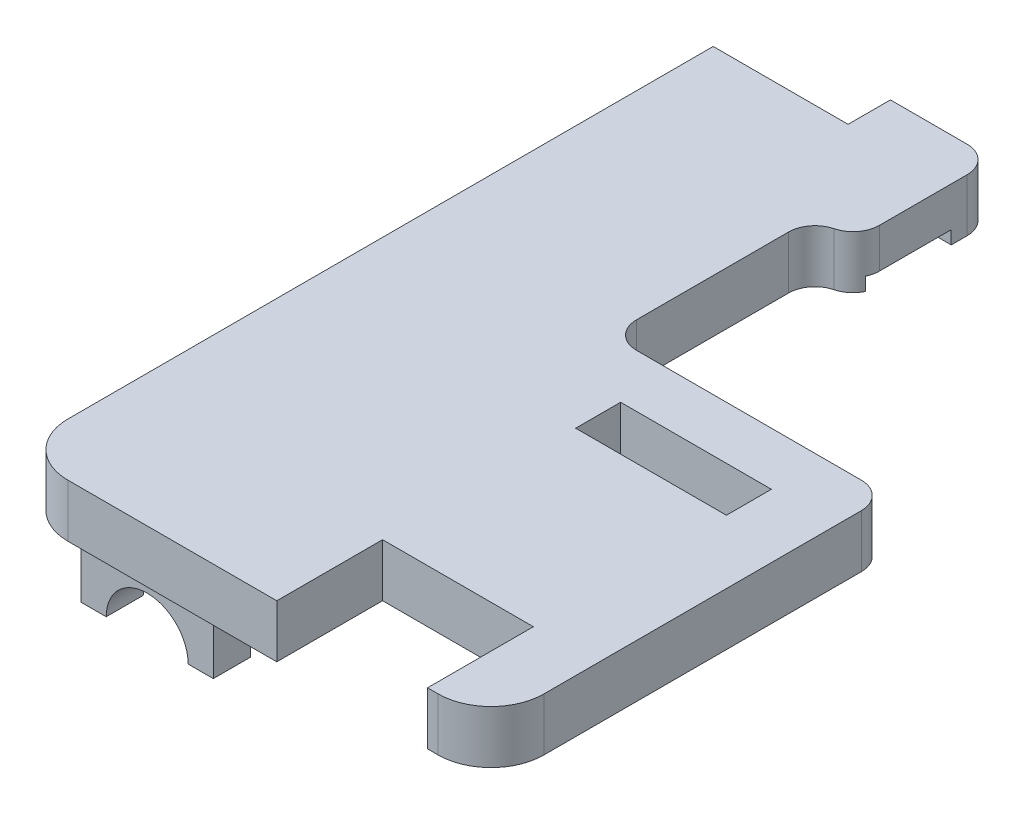
SolidWorks part; units mm, degrees
ref_plane "Front" through (0, 0, 0) normal (0, 0, 1) x (1, 0, 0)
ref_plane "Top" through (0, 0, 0) normal (0, 1, 0) x (1, 0, 0)
ref_plane "Right" through (0, 0, 0) normal (1, 0, 0) x (0, 0, -1)
sketch "Sketch1" plane through (0, 0, 0) normal (0, 1, 0) x (1, 0, 0)
  line L1 (0, 0) -> (18, 0)
  line L2 (0, 0) -> (0, 28)
  line L3 (0, 28) -> (18, 28)
  line L4 (18, 0) -> (18, 28)
  dimension "D1" = 18
  dimension "D2" = 28
extrude "Boss-Extrude1" add sketch "Sketch1" along normal blind 2 contours L2 L3 L4 L1
sketch "Sketch2" plane through (0, 0, 0) normal (0, -1, 0) x (1, 0, 0)
  line L0 (0, -28) -> (0, 0) construction
  line L1 (0, -2.5) -> (5, -2.5)
  line L2 (0, -2.5) -> (0, -3.9)
  line L3 (0, -3.9) -> (5, -3.9)
  line L4 (5, -2.5) -> (5, -3.9)
  line L5 (0, 0) -> (18, 0) construction
  line L6 (0, -16.3) -> (5, -16.3)
  line L7 (0, -16.3) -> (0, -14.9)
  line L8 (0, -14.9) -> (5, -14.9)
  line L9 (5, -16.3) -> (5, -14.9)
  dimension "D1" = 5
  dimension "D2" = 1.4
  dimension "D3" = 1.4
  dimension "D4" = 11
  dimension "D5" = 2.5
extrude "Boss-Extrude2" add sketch "Sketch2" along normal blind 4.25
sketch "Sketch4" plane through (0, 0, 0) normal (0, 0, 1) x (1, 0, 0)
  line L0 (5, -4.25) -> (0, -4.25) construction
  circle A0 centre (2.5, -4.25) radius 1.55
  dimension "D1" = 3.1
extrude "Cut-Extrude1" cut sketch "Sketch4" against normal through all both and the other way through all
fillet "Fillet1" radius 2 1 edges at (0, 1, 0)
sketch "Sketch5" plane through (0, 2, 0) normal (0, 1, 0) x (1, 0, 0)
  line L0 (2, 0) -> (18, 0) construction
  line L1 (9.9, 13) -> (15.6, 13)
  line L2 (9.9, 13) -> (9.9, 11.3)
  line L3 (9.9, 11.3) -> (15.6, 11.3)
  line L4 (15.6, 13) -> (15.6, 11.3)
  line L5 (15.6, 4) -> (9.9, 4)
  line L6 (15.6, 4) -> (15.6, 0)
  line L7 (15.6, 0) -> (9.9, 0)
  line L8 (9.9, 4) -> (9.9, 0)
  line L9 (15.5, 3.9) -> (15.5, 0) construction
  line L10 (10, 3.9) -> (10, 0) construction
  line L11 (15.5, 3.9) -> (10, 3.9) construction
  line L12 (10, 11.4) -> (15.5, 11.4) construction
  line L14 (15.5, 12.9) -> (10, 12.9) construction
  line L15 (5.1, 26.4) -> (0, 26.4)
  line L16 (5.1, 26.4) -> (5.1, 28)
  line L17 (5.1, 28) -> (0, 28)
  line L18 (0, 26.4) -> (0, 28)
  dimension "D1" = 0.1
  dimension "D2" = 0.1
  dimension "D3" = 0.1
  dimension "D4" = 0.1
  dimension "D5" = 0.1
  dimension "D6" = 0.1
  dimension "D7" = 0.1
extrude "Cut-Extrude2" cut sketch "Sketch5" against normal up to surface (2 mm away) up to face at (4.4297, 0, -10.2143)
sketch "Sketch6" plane through (0, 2, 0) normal (0, 1, 0) x (1, 0, 0)
  line L2 (18, 14) -> (20.5, 14)
  line L3 (18, 0) -> (18, 28) construction
  line L4 (17, 15) -> (8.5, 15)
  line L5 (7.5, 16) -> (7.5, 28)
  line L6 (18, 28) -> (5.1, 28) construction
  line L7 (20.5, 14) -> (20.5, 30.5)
  line L8 (20.5, 30.5) -> (7.5, 30.5)
  line L9 (7.5, 30.5) -> (7.5, 28)
  line L10 (15.6, 0) -> (18, 0) construction
  arc A1 (18, 14) -> (17, 15) centre (17, 14) ccw
  arc A2 (8.5, 15) -> (7.5, 16) centre (8.5, 16) cw
  dimension "D2" = 1
  dimension "D4" = 1
  dimension "D1" = 14
  dimension "D3" = 8.5
  dimension "D5" = 2.5
  dimension "D6" = 2.5
extrude "Cut-Extrude3" cut sketch "Sketch6" against normal through all and the other way through all
fillet "Fillet2" radius 2 1 edges at (18, 1, 0)
sketch "Sketch8" plane through (7.5, 0, 0) normal (1, 0, 0) x (0, 0, -1)
  line L0 (16, 2) -> (28, 2) construction
  line L1 (28, 0) -> (22.75, 0)
  line L2 (28, 0) -> (28, 2)
  line L3 (28, 2) -> (22.75, 2)
  line L4 (22.75, 0) -> (22.75, 2)
  dimension "D1" = 5.25
extrude "Boss-Extrude3" add sketch "Sketch8" along normal up to vertex (1.5 mm away)
fillet "Fillet3" radius 1 2 edges at (9, 1, -28) (7.5, 1, -22.75)
fillet "Fillet4" radius 1 1 edges at (9, 1, -22.75)
sketch "Sketch7" plane through (0, 0, 0) normal (-1, 0, 0) x (0, 0, 1)
  line L0 (-26.4, 0) -> (-16.3, 0) construction
  line L1 (-23.25, 0) -> (-26.4, 0)
  line L2 (-23.25, 0) -> (-23.25, 0.5)
  line L3 (-23.25, 0.5) -> (-26.4, 0.5)
  line L4 (-26.4, 0) -> (-26.4, 0.5)
  line L6 (-26.4, 0) -> (-26.4, 2) construction
  dimension "D1" = 3.15
  dimension "D2" = 0.5
extrude "Cut-Extrude4" cut sketch "Sketch7" against normal through all
sketch "Sketch9" plane through (0, 0, -3.9) normal (0, 0, -1) x (-1, 0, 0)
  line L1 (0, 0) -> (-1, 0)
  line L2 (0, 0) -> (0, -1.2567)
  line L4 (-1, 0) -> (-1, -0.65)
  arc A0 (0, -1.2567) -> (-1, -0.65) centre (-2.5, -4.25) ccw
  dimension "D1" = 3.9
  dimension "D2" = 1
extrude "Boss-Extrude4" add sketch "Sketch9" along normal up to next
sketch "Sketch10" plane through (0, 0, -16.3) normal (0, 0, -1) x (-1, 0, 0)
  line L0 (-5, -1.5) -> (-4.075, -2.15)
  line L1 (0, 0) -> (-5, 0)
  line L2 (0, 0) -> (0, -3.4496)
  line L4 (-5, 0) -> (-5, -1.5)
  line L6 (-5, -4.25) -> (-5, 0) construction
  arc A0 (0, -3.4496) -> (-4.075, -2.15) centre (-2.5, -4.25) ccw
  dimension "D1" = 5.25
  dimension "D2" = 1.5
  dimension "D3" = 2.15
extrude "Boss-Extrude6" add sketch "Sketch10" along normal offset from surface (6.45 mm away) 0.5 up to face at (4.4499, 0.25, -23.25)
sketch "Sketch11" plane through (0, 0, -22.75) normal (0, 0, -1) x (-1, 0, 0)
  line L0 (-4.075, -2.15) -> (-3.1841, -2.776)
  line L1 (-4.075, -2.15) -> (-5, -1.5) construction
  line L2 (-4.075, -2.15) -> (-5, -1.5) construction
  line L3 (0, -4.25) -> (-0.95, -4.25) construction
  line L4 (0, -4.25) -> (0, -3.4496) construction
  line L5 (0, -4.25) -> (-0.875, -4.25)
  line L6 (0, -4.25) -> (0, -3.4496)
  arc A0 (-0.875, -4.25) -> (-3.1841, -2.776) centre (-2.5, -4.25) ccw
  arc A1 (0, -3.4496) -> (-4.075, -2.15) centre (-2.5, -4.25) ccw construction
  arc A2 (0, -3.4496) -> (-4.075, -2.15) centre (-2.5, -4.25) ccw
  dimension "D1" = 3.25
extrude "Boss-Extrude7" add sketch "Sketch11" against normal offset from surface (4.7 mm away) 1.75 up to face at (2.6771, -3.0713, -16.3)
fillet "Fillet6" [suppressed] radius 2
fillet "Fillet7" radius 2 1 edges at (1, 0, -9.4)
fillet "Fillet8" radius 1.85 1 edges at (2.5, 0, -2.5)
